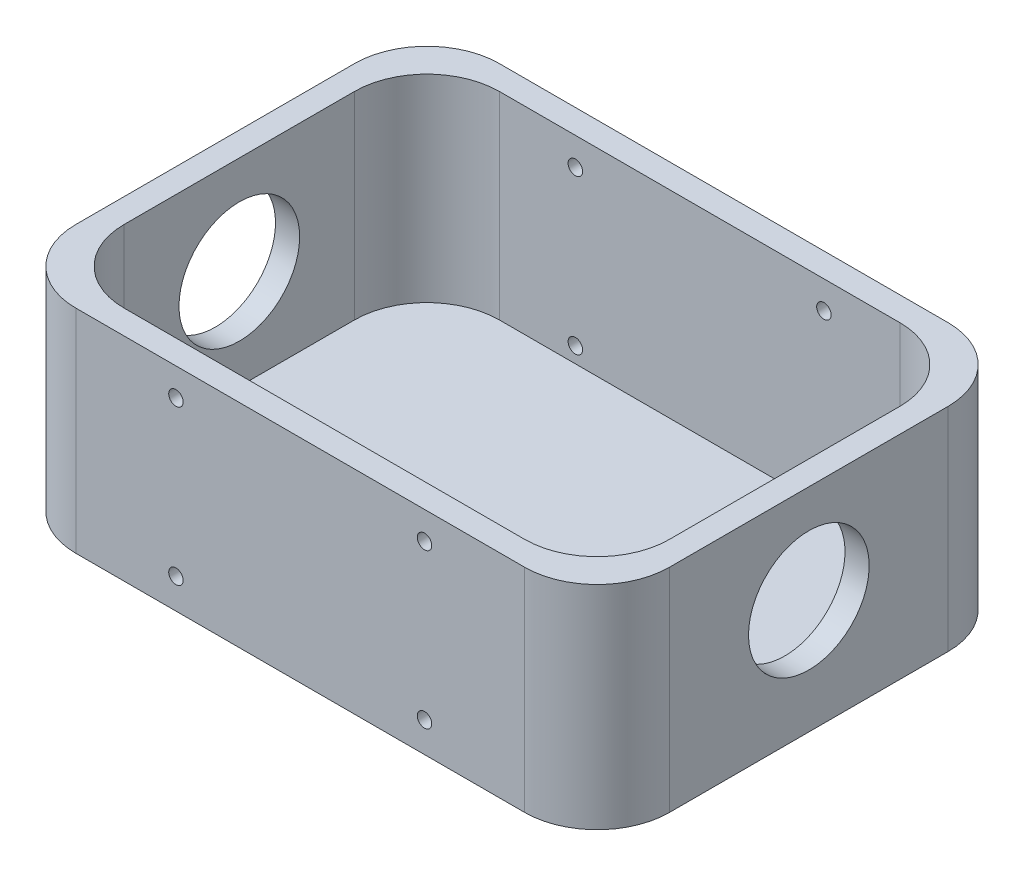
SolidWorks part; units mm, degrees
material "ABS"
ref_plane "Front Plane" through (0, 0, 0) normal (0, 0, 1) x (1, 0, 0)
ref_plane "Top Plane" through (0, 0, 0) normal (0, 1, 0) x (1, 0, 0)
ref_plane "Right Plane" through (0, 0, 0) normal (1, 0, 0) x (0, 0, -1)
sketch "Sketch1" plane through (0, 0, 0) normal (0, 1, 0) x (1, 0, 0)
  line L0 (-61.5, -43.875) -> (61.5, -43.875)
  line L1 (-61.5, -43.875) -> (-61.5, 43.875)
  line L2 (61.5, -43.875) -> (61.5, 43.875)
  line L3 (-61.5, 43.875) -> (61.5, 43.875)
  line L4 (-61.5, -43.875) -> (61.5, 43.875) construction
  line L5 (61.5, -43.875) -> (-61.5, 43.875) construction
  line L10 (-56.5, -38.875) -> (-56.5, 38.875)
  line L11 (-56.5, 38.875) -> (56.5, 38.875)
  line L12 (56.5, -38.875) -> (56.5, 38.875)
  line L13 (-56.5, -38.875) -> (56.5, -38.875)
  point P1 (0, 0)
  dimension "D1" = 123
  dimension "D2" = 87.75
  dimension "D3" = 5
extrude "Boss-Extrude1" add sketch "Sketch1" along normal blind 44
extrude "Boss-Extrude2" add sketch "Sketch1<3>" along normal blind 3 contours L10 L13 L12 L11 region at (0, 0, 0)
sketch "Sketch1<3>" plane through (0, 0, 0) normal (0, 1, 0) x (1, 0, 0) same geometry as "Sketch1"
fillet "Fillet1" radius 15 1 edges at (-61.5, 22, 43.875) type face fillet first side face at (0, 22, 43.875) second side face at (-61.5, 22, 0)
fillet "Fillet2" radius 15 1 edges at (-61.5, 22, -43.875) type face fillet first side face at (-61.5, 22, -7.5) second side face at (0, 22, -43.875)
fillet "Fillet3" radius 15 1 edges at (61.5, 22, -43.875) type face fillet first side face at (7.5, 22, -43.875) second side face at (61.5, 22, 0)
fillet "Fillet4" radius 15 1 edges at (61.5, 22, 43.875) type face fillet first side face at (61.5, 22, 7.5) second side face at (7.5, 22, 43.875)
fillet "Fillet5" radius 15 1 edges at (-56.5, 23.5, -38.875) type face fillet first side face at (0, 23.5, -38.875) second side face at (-56.5, 23.5, 0)
fillet "Fillet6" radius 15 1 edges at (-56.5, 23.5, 38.875) type face fillet first side face at (0, 23.5, 38.875) second side face at (-56.5, 23.5, 7.5)
fillet "Fillet7" radius 15 1 edges at (56.5, 23.5, -38.875) type face fillet first side face at (7.5, 23.5, -38.875) second side face at (56.5, 23.5, 0)
fillet "Fillet8" radius 15 1 edges at (56.5, 23.5, 38.875) type face fillet first side face at (56.5, 23.5, 7.5) second side face at (7.5, 23.5, 38.875)
sketch "Sketch2" plane through (0, 0, -43.875) normal (0, 0, -1) x (-1, 0, 0)
  line L0 (0, 0) -> (0, 6.25)
  line L1 (-46.5, 0) -> (46.5, 0) construction
  line L2 (0, 6.25) -> (-25.75, 6.25)
  circle A0 centre (-25.75, 6.25) radius 1.5
  dimension "D3" = 3
  dimension "D1" = 6.25
  dimension "D2" = 25.75
extrude "Cut-Extrude1" cut sketch "Sketch2" against normal through all contours A0
mirror "Mirror1" about plane through (0, 0, 0) normal (1, 0, 0) of "Cut-Extrude1"
pattern_linear "LPattern2" count 2 spacing 32 along (0, 1, 0) of "Mirror1"
sketch "Sketch3" plane through (-61.5, 0, 0) normal (-1, 0, 0) x (0, 0, 1)
  line L0 (0, 44) -> (0, 23.62)
  line L1 (-28.875, 44) -> (28.875, 44) construction
  circle A0 centre (0, 23.62) radius 12.5
  dimension "D2" = 25
  dimension "D1" = 20.38
extrude "Cut-Extrude2" cut sketch "Sketch3" against normal through all contours A0 region at (-61.5, 15.0312, -8.5888)
